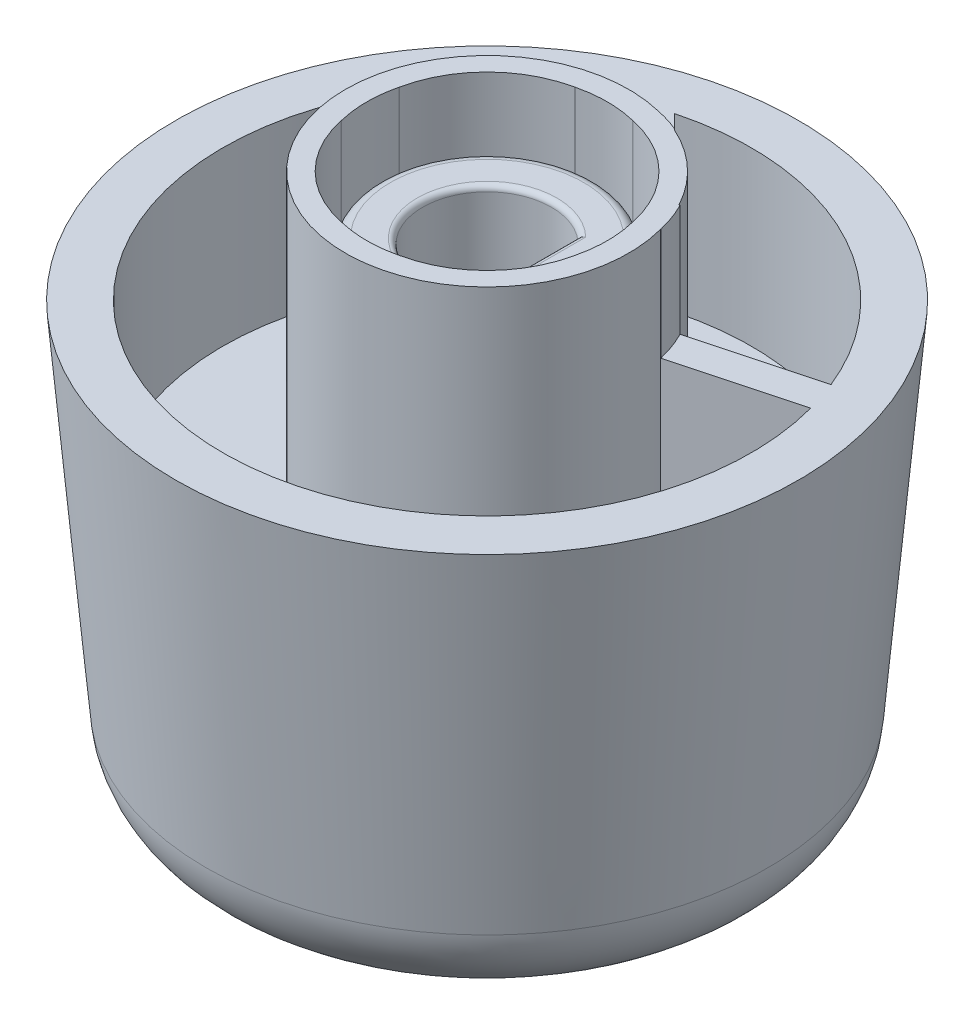
SolidWorks part; units mm, degrees
ref_plane "Front Plane" through (0, 0, 0) normal (0, 0, 1) x (1, 0, 0)
ref_plane "Top Plane" through (0, 0, 0) normal (0, 1, 0) x (1, 0, 0)
ref_plane "Right Plane" through (0, 0, 0) normal (1, 0, 0) x (0, 0, -1)
sketch "Sketch1" plane through (0, 0, 0) normal (0, 1, 0) x (1, 0, 0)
  line L0 (2, 2.2361) -> (2, -2.2361)
  arc A0 (2, 2.2361) -> (2, -2.2361) centre (0, 0) ccw
  circle A1 centre (0, 0) radius 5
  dimension "D1" = 6
  dimension "D3" = 2
  dimension "D2" = 2
extrude "Boss-Extrude1" add sketch "Sketch1" along normal blind 2.5
sketch "Sketch2" plane through (0, 0, 0) normal (0, -1, 0) x (1, 0, 0)
  line L0 (-3, 0) -> (-6.6, 0) construction
  line L1 (-6.3054, 1.95) -> (-5.2495, 1.95)
  line L2 (-6.3054, -1.95) -> (-5.2495, -1.95)
  line L3 (-1.95, 6.3054) -> (-1.95, 5.2495)
  line L4 (1.95, 6.3054) -> (1.95, 5.2495)
  line L5 (6.3054, 1.95) -> (5.2495, 1.95)
  line L6 (6.3054, -1.95) -> (5.2495, -1.95)
  line L7 (1.95, -6.3054) -> (1.95, -5.2495)
  line L8 (-1.95, -6.3054) -> (-1.95, -5.2495)
  circle A0 centre (0, 0) radius 6.6 construction
  arc A1 (2, 2.2361) -> (2, -2.2361) centre (0, 0) ccw construction
  arc A2 (-6.3054, 1.95) -> (-6.3054, -1.95) centre (0, 0) ccw
  arc A3 (-5.2495, 1.95) -> (-5.2495, -1.95) centre (0, 0) ccw
  arc A4 (1.95, 5.2495) -> (-1.95, 5.2495) centre (0, 0) ccw
  arc A5 (1.95, 6.3054) -> (-1.95, 6.3054) centre (0, 0) ccw
  arc A6 (5.2495, -1.95) -> (5.2495, 1.95) centre (0, 0) ccw
  arc A7 (6.3054, -1.95) -> (6.3054, 1.95) centre (0, 0) ccw
  arc A8 (-1.95, -5.2495) -> (1.95, -5.2495) centre (0, 0) ccw
  arc A9 (-1.95, -6.3054) -> (1.95, -6.3054) centre (0, 0) ccw
  point P11 (-6.6, 0)
  point P15 (-5.6, 0)
  point P31 (0, 0)
  dimension "D1" = 3.6
  dimension "D2" = 3.9
  dimension "D3" = 3.9
  dimension "D4" = 1
  dimension "D5" = 4
extrude "Boss-Extrude2" add sketch "Sketch2" against normal blind 5.2 separate body
fillet "Fillet1" radius 0.5 4 edges at (1.95, 2.6, -6.3054) (-1.95, 2.6, -6.3054) (1.95, 2.6, -5.2495) (-1.95, 2.6, -5.2495)
fillet "Fillet2" radius 0.5 4 edges at (6.3054, 2.6, 1.95) (6.3054, 2.6, -1.95) (5.2495, 2.6, -1.95) (5.2495, 2.6, 1.95)
fillet "Fillet3" radius 0.5 4 edges at (-1.95, 2.6, 6.3054) (-1.95, 2.6, 5.2495) (1.95, 2.6, 6.3054) (1.95, 2.6, 5.2495)
fillet "Fillet4" radius 0.5 4 edges at (-6.3054, 2.6, 1.95) (-5.2495, 2.6, -1.95) (-6.3054, 2.6, -1.95) (-5.2495, 2.6, 1.95)
sketch "Sketch3" plane through (0, 0, 0) normal (0, 1, 0) x (1, 0, 0)
  circle A0 centre (0, 0) radius 14.5
  dimension "D1" = 29
extrude "Boss-Extrude3" add sketch "Sketch3" against normal blind 20
sketch "Sketch4" plane through (0, 0, 0) normal (0, 1, 0) x (1, 0, 0)
  circle A0 centre (0, 0) radius 14.5
extrude "Cut-Extrude2" cut sketch "Sketch4" against normal blind 20 draft 5 flip side to cut draft outward yes
fillet "Fillet5" radius 4 1 edges at (0, -20, 12.7502)
sketch "Sketch5" plane through (0, 0, 0) normal (0, 1, 0) x (1, 0, 0)
  line L2 (2, -2.2361) -> (2, 2.2361)
  line L3 (2, -2.2361) -> (2, 2.2361)
  arc A2 (2, 2.2361) -> (2, -2.2361) centre (0, 0) ccw
  arc A3 (2, 2.2361) -> (2, -2.2361) centre (0, 0) ccw
  dimension "D1" = 0
extrude "Cut-Extrude3" cut sketch "Sketch5" against normal blind 14
fillet "Fillet6" radius 0.25 2 edges at (-3, 2.5, 0) (2, 2.5, 0)
fillet "Fillet7" radius 0.5 1 edges at (0, 2.5, 5)
sketch "Sketch6" plane through (0, 0, 0) normal (0, 1, 0) x (1, 0, 0)
  circle A0 centre (0, 0) radius 6.6
  circle A1 centre (0, 0) radius 12.3
  circle A2 centre (0, 0) radius 14.5 construction
  arc A3 (1.5689, 6.4108) -> (-1.5689, 6.4108) centre (0, 0) ccw construction
  dimension "D1" = 2.2
extrude "Cut-Extrude4" cut sketch "Sketch6" against normal blind 8
sketch "Sketch7" plane through (0, -8, 0) normal (0, 1, 0) x (1, 0, 0)
  line L0 (0, 0) -> (12.3, 0) construction
  line L1 (0, 0) -> (11.8809, 3.1835) construction
  line L2 (6.3751, 1.7082) -> (11.8809, 3.1835)
  line L3 (5.8201, 3.1124) -> (11.404, 4.6086)
  line L4 (0, 0) -> (9.9124, 10.3319) construction
  line L5 (0, 0) -> (0, 14.5) construction
  line L6 (2.6979, 6.0234) -> (-3.1646, 11.8859)
  line L7 (-4.747, 11.347) -> (0, 6.6)
  circle A0 centre (0, 0) radius 12.3 construction
  circle A1 centre (0, 0) radius 6.6 construction
  circle A2 centre (0, 0) radius 12.3 construction
  arc A3 (5.8201, 3.1124) -> (6.3751, 1.7082) centre (0, 0) cw
  arc A4 (11.404, 4.6086) -> (11.8809, 3.1835) centre (0, 0) cw
  arc A5 (6.4108, 1.5689) -> (1.5689, 6.4108) centre (0, 0) ccw construction
  circle A6 centre (0, 0) radius 14.5 construction
  arc A7 (-4.747, 11.347) -> (-3.1646, 11.8859) centre (0, 0) cw
  arc A8 (0, 6.6) -> (2.6979, 6.0234) centre (0, 0) cw
  dimension "D3" = 1.5
  dimension "D1" = 15
  dimension "D2" = 1.5
  dimension "D4" = 45
extrude "Boss-Extrude4" add sketch "Sketch7" along normal up to surface (8 mm away) up to face at (0, 0, 5)
sketch "Sketch8" plane through (0, 0, 0) normal (0, 1, 0) x (1, 0, 0)
  arc A0 (-6.4108, 1.5689) -> (-1.5689, 6.4108) centre (-0.2722, 0.2722) cw
  arc A1 (-5.4395, 1.3311) -> (-1.3311, 5.4395) centre (-0.2722, 0.2722) cw
  arc A2 (-1.5689, 6.4108) -> (-1.3311, 5.4395) centre (-1.45, 5.9252) ccw
  arc A3 (-6.4108, 1.5689) -> (-5.4395, 1.3311) centre (-5.9252, 1.45) cw
  arc A4 (1.3311, 5.4395) -> (5.4395, 1.3311) centre (0.2722, 0.2722) cw
  arc A5 (1.5689, 6.4108) -> (1.3311, 5.4395) centre (1.45, 5.9252) cw
  arc A6 (1.5689, 6.4108) -> (6.4108, 1.5689) centre (0.2722, 0.2722) cw
  arc A7 (6.4108, 1.5689) -> (5.4395, 1.3311) centre (5.9252, 1.45) ccw
  arc A8 (5.4395, -1.3311) -> (1.3311, -5.4395) centre (0.2722, -0.2722) cw
  arc A9 (6.4108, -1.5689) -> (5.4395, -1.3311) centre (5.9252, -1.45) cw
  arc A10 (6.4108, -1.5689) -> (1.5689, -6.4108) centre (0.2722, -0.2722) cw
  arc A11 (1.5689, -6.4108) -> (1.3311, -5.4395) centre (1.45, -5.9252) ccw
  arc A12 (-1.3311, -5.4395) -> (-5.4395, -1.3311) centre (-0.2722, -0.2722) cw
  arc A13 (-1.5689, -6.4108) -> (-1.3311, -5.4395) centre (-1.45, -5.9252) cw
  arc A14 (-1.5689, -6.4108) -> (-6.4108, -1.5689) centre (-0.2722, -0.2722) cw
  arc A15 (-6.4108, -1.5689) -> (-5.4395, -1.3311) centre (-5.9252, -1.45) ccw
  point P39 (0, 0)
  arc M2 (1.5689, 6.4108) -> (1.95, 5.9252) centre (1.45, 5.9252) cw
  arc M3 (1.95, 5.9252) -> (1.3311, 5.4395) centre (1.45, 5.9252) cw
  arc M5 (-1.3311, 5.4395) -> (-1.95, 5.9252) centre (-1.45, 5.9252) cw
  arc M6 (-1.95, 5.9252) -> (-1.5689, 6.4108) centre (-1.45, 5.9252) cw
  arc M7 (-1.5689, 6.4108) -> (-6.4108, 1.5689) centre (0, 0) ccw
  arc M8 (-6.4108, 1.5689) -> (-5.9252, 1.95) centre (-5.9252, 1.45) cw
  arc M9 (-5.9252, 1.95) -> (-5.4395, 1.3311) centre (-5.9252, 1.45) cw
  arc M11 (-5.4395, -1.3311) -> (-5.9252, -1.95) centre (-5.9252, -1.45) cw
  arc M12 (-5.9252, -1.95) -> (-6.4108, -1.5689) centre (-5.9252, -1.45) cw
  arc M13 (-6.4108, -1.5689) -> (-1.5689, -6.4108) centre (0, 0) ccw
  arc M14 (-1.5689, -6.4108) -> (-1.95, -5.9252) centre (-1.45, -5.9252) cw
  arc M15 (-1.95, -5.9252) -> (-1.3311, -5.4395) centre (-1.45, -5.9252) cw
  arc M17 (1.3311, -5.4395) -> (1.95, -5.9252) centre (1.45, -5.9252) cw
  arc M18 (1.95, -5.9252) -> (1.5689, -6.4108) centre (1.45, -5.9252) cw
  arc M19 (1.5689, -6.4108) -> (6.4108, -1.5689) centre (0, 0) ccw
  arc M20 (6.4108, -1.5689) -> (5.9252, -1.95) centre (5.9252, -1.45) cw
  arc M21 (5.9252, -1.95) -> (5.4395, -1.3311) centre (5.9252, -1.45) cw
  arc M23 (5.4395, 1.3311) -> (5.9252, 1.95) centre (5.9252, 1.45) cw
  arc M24 (5.9252, 1.95) -> (6.4108, 1.5689) centre (5.9252, 1.45) cw
  arc M25 (6.4108, 1.5689) -> (6.3751, 1.7082) centre (0, 0) ccw
  line M26 (6.3751, 1.7082) -> (11.8809, 3.1835)
  line M30 (11.404, 4.6086) -> (5.8201, 3.1124)
  arc M31 (5.8201, 3.1124) -> (2.6979, 6.0234) centre (0, 0) ccw
  line M32 (2.6979, 6.0234) -> (-3.1646, 11.8859)
  dimension "D1" = 4
extrude "Boss-Extrude5" add sketch "Sketch8" along normal up to surface (5.2 mm away) contours A6 A4 M2 M3 M23 M24 M25 M26 M30 M31 M32 | A8 M21 M17 M18 M19 M20 | A12 M15 M11 M12 M13 M14 | A1 M9 M5 M6 M7 M8 region at (-4.171, 0, -4.171) region at (4.1771, 0, -4.1676) region at (4.171, 0, 4.171) region at (-4.171, 0, 4.171) up to face at (5.9552, 5.2, 0)
